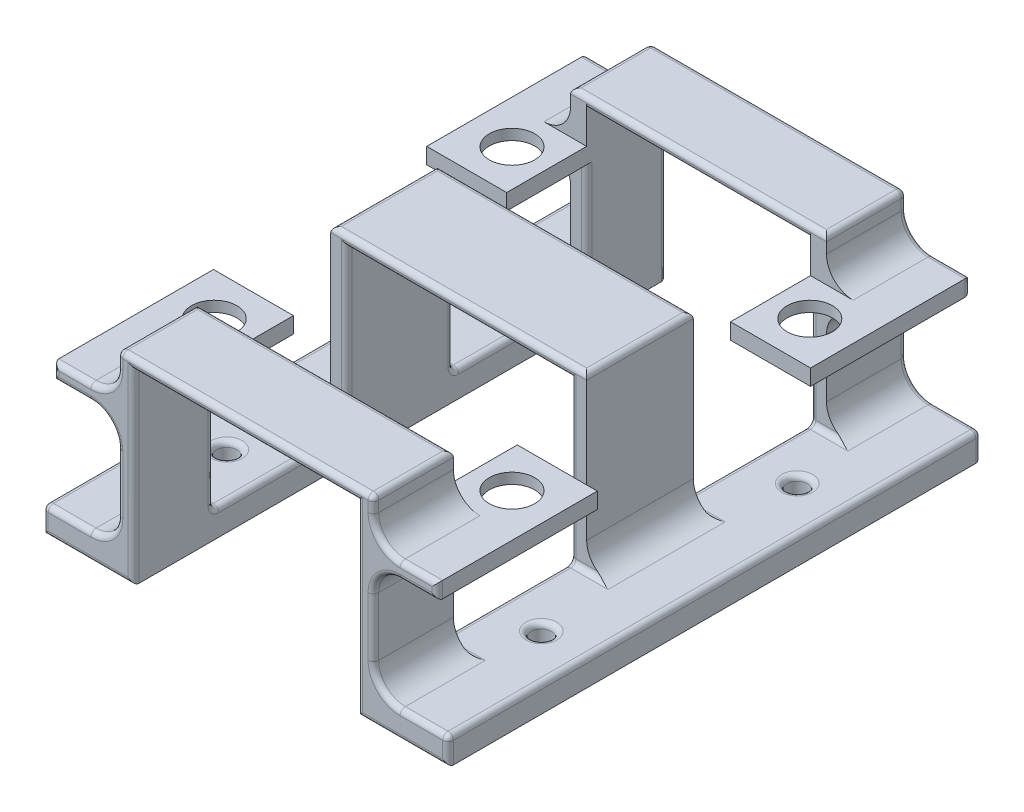
SolidWorks part; units mm, degrees
ref_plane "Front Plane" through (0, 0, 0) normal (0, 0, 1) x (1, 0, 0)
ref_plane "Top Plane" through (0, 0, 0) normal (0, 1, 0) x (1, 0, 0)
ref_plane "Right Plane" through (0, 0, 0) normal (1, 0, 0) x (0, 0, -1)
sketch "Sketch1" plane through (0, 0, 0) normal (0, 1, 0) x (1, 0, 0)
  line L0 (0, 36.3483) -> (0, -47.9367) construction
  line L1 (-42.1108, 0) -> (36.0317, 0) construction
  line L2 (-44.7071, 24) -> (37.8047, 24) construction
  line L3 (-29.5, 42.1741) -> (-29.5, -15.4512) construction
  line L4 (-21, 42.8074) -> (-21, -47.9367) construction
  line L5 (38, -50) -> (21, -50)
  line L10 (-38, -50) -> (-21, -50)
  line L11 (21, -50) -> (21, 50)
  line L12 (-38, -50) -> (-38, 50)
  line L13 (-38, 50) -> (-21, 50)
  line L14 (-21, -50) -> (-21, 50)
  line L15 (-38, -50) -> (-21, 50) construction
  line L16 (-38, 50) -> (-21, -50) construction
  line L17 (38, 50) -> (21, 50)
  line L18 (38, -50) -> (38, 50)
  circle A0 centre (-29.5, 24) radius 1.9
  circle A1 centre (-29.5, -24) radius 1.9
  circle A2 centre (29.5, 24) radius 1.9
  circle A3 centre (29.5, -24) radius 1.9
  point P9 (-29.5, 24)
  point P10 (-29.5, 0)
  dimension "D5" = 3.8
  dimension "D1" = 24
  dimension "D2" = 29.5
  dimension "D3" = 21
  dimension "D4" = 100
extrude "Boss-Extrude1" add sketch "Sketch1" along normal blind 5
sketch "Sketch2" plane through (0, 5, 0) normal (0, 1, 0) x (1, 0, 0)
  line L0 (-24, 50) -> (-24, -50) construction
  line L1 (-21, 50) -> (-38, 50) construction
  line L2 (-38, -50) -> (-21, -50) construction
  line L3 (-21, -50) -> (-21, 50) construction
  line L4 (0, 61.7817) -> (0, -74.2778) construction
  line L5 (-21, 50) -> (-24, 50)
  line L6 (-21, 50) -> (-21, 35)
  line L7 (-21, 35) -> (-24, 35)
  line L8 (-24, 50) -> (-24, 35)
  line L9 (-21, -50) -> (-24, -50)
  line L10 (-21, -50) -> (-21, -35)
  line L11 (-21, -35) -> (-24, -35)
  line L12 (-24, -50) -> (-24, -35)
  line L13 (-24, 10) -> (-21, 10)
  line L14 (-24, 10) -> (-24, -10)
  line L15 (-24, -10) -> (-21, -10)
  line L16 (-21, 10) -> (-21, -10)
  line L17 (21, -35) -> (24, -35)
  line L18 (24, -50) -> (24, -35)
  line L19 (21, -50) -> (24, -50)
  line L20 (21, -50) -> (21, -35)
  line L21 (24, -10) -> (21, -10)
  line L22 (21, 10) -> (21, -10)
  line L23 (24, 10) -> (21, 10)
  line L24 (24, 10) -> (24, -10)
  line L25 (21, 35) -> (24, 35)
  line L26 (24, 50) -> (24, 35)
  line L27 (21, 50) -> (24, 50)
  line L28 (21, 50) -> (21, 35)
  point P20 (-24, 0)
  dimension "D1" = 3
  dimension "D2" = 15
  dimension "D3" = 15
  dimension "D4" = 20
extrude "Boss-Extrude2" add sketch "Sketch2" along normal blind 30
sketch "Sketch3" plane through (0, 35, 0) normal (0, 1, 0) x (1, 0, 0)
  line L1 (-24, 50) -> (24, 50)
  line L2 (-24, 50) -> (-24, 35)
  line L3 (-24, 35) -> (24, 35)
  line L4 (24, 50) -> (24, 35)
  line L5 (-24, 10) -> (24, 10)
  line L6 (-24, 10) -> (-24, -10)
  line L7 (-24, -10) -> (24, -10)
  line L8 (24, 10) -> (24, -10)
  line L9 (-24, -35) -> (24, -35)
  line L10 (-24, -35) -> (-24, -50)
  line L11 (-24, -50) -> (24, -50)
  line L12 (24, -35) -> (24, -50)
extrude "Boss-Extrude3" add sketch "Sketch3" along normal blind 2
ref_plane "Plane1" through (0, 27, 0) normal (0, 1, 0) x (1, 0, 0)
sketch "Sketch4" plane through (0, 27, 0) normal (0, 1, 0) x (1, 0, 0)
  line L6 (-24, -50) -> (-24, -35) construction
  line L7 (0, 50) -> (0, -50) construction
  line L8 (-24, -50) -> (-36, -50)
  line L9 (-24, -50) -> (-24, -35)
  line L10 (-26, -20) -> (-36, -20)
  line L11 (-36, -50) -> (-36, -20)
  line L12 (24, 50) -> (-24, 50) construction
  line L13 (-24, -50) -> (24, -50) construction
  line L14 (-38, 0) -> (38, 0) construction
  line L15 (-38, 50) -> (-38, -50) construction
  line L16 (38, -50) -> (38, 50) construction
  line L17 (0, 0) -> (46.7381, 46.7381) construction
  line L18 (0, 0) -> (-51.7743, -51.7743) construction
  line L19 (-26, 20) -> (-36, 20)
  line L20 (-26, -20) -> (-21, -20)
  line L22 (-24, -35) -> (-21, -35)
  line L23 (-21, -20) -> (-21, -35)
  line L25 (-26, -20) -> (-26, -15.9377) construction
  line L26 (-36, 50) -> (-36, 20)
  line L27 (-24, 50) -> (-36, 50)
  line L28 (-24, 50) -> (-24, 35)
  line L29 (-24, 35) -> (-21, 35)
  line L30 (-21, 20) -> (-21, 35)
  line L31 (-26, 20) -> (-21, 20)
  line L32 (26, -20) -> (36, -20)
  line L33 (36, -50) -> (36, -20)
  line L34 (24, -50) -> (36, -50)
  line L35 (24, -50) -> (24, -35)
  line L36 (24, -35) -> (21, -35)
  line L37 (21, -20) -> (21, -35)
  line L38 (26, -20) -> (21, -20)
  line L39 (26, 20) -> (21, 20)
  line L40 (21, 20) -> (21, 35)
  line L41 (24, 35) -> (21, 35)
  line L42 (24, 50) -> (24, 35)
  line L43 (24, 50) -> (36, 50)
  line L44 (36, 50) -> (36, 20)
  line L45 (26, 20) -> (36, 20)
  circle A0 centre (-27.9307, -27.9307) radius 4.25
  circle A1 centre (-27.9307, 27.9307) radius 4.25
  circle A2 centre (27.9307, -27.9307) radius 4.25
  circle A3 centre (27.9307, 27.9307) radius 4.25
  dimension "D3" = 8.5
  dimension "D1" = 12
  dimension "D2" = 30
  dimension "D4" = 39.5
extrude "Boss-Extrude4" add sketch "Sketch4" along normal blind 2 and the other way blind 1
sketch "Sketch5" plane through (0, 26, 0) normal (0, -1, 0) x (1, 0, 0)
  circle A0 centre (-27.9307, -27.9307) radius 6.5
  circle A1 centre (-27.9307, 27.9307) radius 6.5
  circle A2 centre (27.9307, 27.9307) radius 6.5
  circle A3 centre (27.9307, -27.9307) radius 6.5
  dimension "D1" = 13
  dimension "D2" = 13
  dimension "D3" = 13
  dimension "D4" = 13
extrude "Cut-Extrude1" cut sketch "Sketch5" against normal blind 1
fillet "Fillet1" radius 5 14 edges at (-24, 26, 42.5) (-24, 29, 42.5) (-24, 26, -42.5) (-24, 29, -42.5) (24, 29, -42.5) (24, 29, 42.5) (24, 26, 42.5) (24, 26, -42.5) (-24, 5, 42.5) (-24, 5, 0) (-24, 5, -42.5) (24, 5, 0) (24, 5, -42.5) (24, 5, 42.5)
fillet "Fillet2" radius 1 90 edges at (-21, 15.5, -35) (-21, 20, -10) (-21, 20, 10) (-21, 15.5, 35) (21, 15.5, -35) (21, 20, -10) (21, 15.5, 35) (21, 20, 10) (-38, 2.5, 50) (-25.4645, 6.4645, 50) (-24, 15.5, 50) (-25.4645, 24.5355, 50) (-32.5, 26, 50) (-36, 27.5, 50) (-32.5, 29, 50) (-25.4645, 30.4645, 50) (24, 35.5, 50) (25.4645, 30.4645, 50) (32.5, 29, 50) (36, 27.5, 50) (32.5, 26, 50) (25.4645, 24.5355, 50) (24, 15.5, 50) (25.4645, 6.4645, 50) (38, 2.5, 50) (29.5, 0, 50) (21, 17.5, 50) (0, 35, 50) (-21, 17.5, 50) (-29.5, 0, 50) (-21, 17.5, -50) (0, 35, -50) (21, 17.5, -50) (29.5, 0, -50) (38, 2.5, -50) (25.4645, 6.4645, -50) (24, 15.5, -50) (25.4645, 24.5355, -50) (32.5, 26, -50) (36, 27.5, -50) (32.5, 29, -50) (25.4645, 30.4645, -50) (-24, 35.5, -50) (-25.4645, 30.4645, -50) (-32.5, 29, -50) (-36, 27.5, -50) (-32.5, 26, -50) (-25.4645, 24.5355, -50) (-24, 15.5, -50) (-25.4645, 6.4645, -50) (-38, 2.5, -50) (-29.5, 0, -50) (0, 37, 35) (24, 37, 42.5) (0, 37, 50) (-24, 37, 42.5) (0, 37, -10) (24, 37, 0) (0, 37, 10) (-24, 37, 0) (0, 37, -50) (24, 37, -42.5) (0, 37, -35) (-24, 37, -42.5) (-38, 5, 0) (-33.5, 5, -50) (-25, 5, -35) (-21, 5, -22.5) (-25, 5, -10) (-25, 5, 10) (-21, 5, 22.5) (-25, 5, 35) (-33.5, 5, 50) (-29.5, 5, -22.1) (-29.5, 5, 22.1) (21, 5, -22.5) (25, 5, -35) (33.5, 5, -50) (38, 5, 0) (33.5, 5, 50) (25, 5, 35) (21, 5, 22.5) (25, 5, 10) (25, 5, -10) (29.5, 5, 25.9) (29.5, 5, -25.9) (0, 35, 35) (0, 35, -35) (0, 35, -10) (0, 35, 10)
